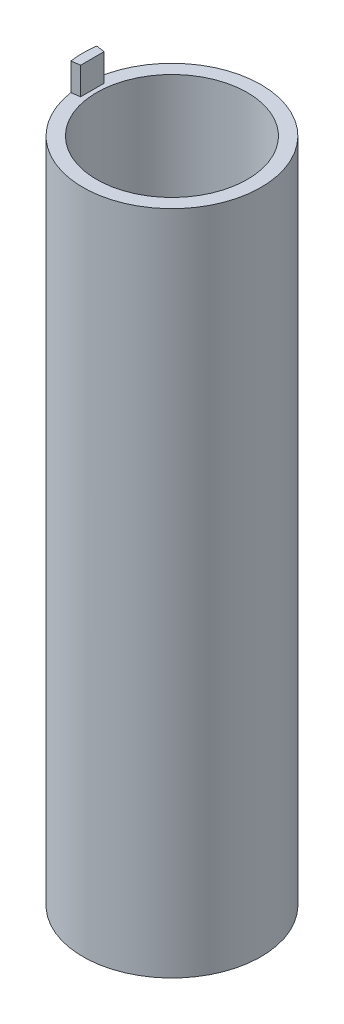
SolidWorks part; units mm, degrees
ref_plane "Front Plane" through (0, 0, 0) normal (0, 0, 1) x (1, 0, 0)
ref_plane "Top Plane" through (0, 0, 0) normal (0, 1, 0) x (1, 0, 0)
ref_plane "Right Plane" through (0, 0, 0) normal (1, 0, 0) x (0, 0, -1)
sketch "Sketch1" plane through (0, 0, 0) normal (0, 1, 0) x (1, 0, 0)
  circle A0 centre (0, 0) radius 17.4625
  circle A1 centre (0, 0) radius 20.6375
  dimension "D1" = 34.925
  dimension "D2" = 3.175
extrude "Boss-Extrude1" add sketch "Sketch1" along normal blind 152.4
sketch "Sketch2" plane through (0, 0, 0) normal (0, -1, 0) x (-1, 0, 0)
  circle A0 centre (0, 0) radius 20.6375
  circle A1 centre (0, 0) radius 20.6375 construction
extrude "Boss-Extrude2" add sketch "Sketch2" along normal blind 2
sketch "Sketch3" plane through (0, 0, 0) normal (0, 0, 1) x (1, 0, 0)
  line L0 (-20.6375, 152.4) -> (-20.6375, 158.75)
  line L1 (-20.6375, 158.75) -> (-18.6375, 158.75)
  line L2 (0, 152.4) -> (0, 163.3315) construction
  line L3 (17.4625, 152.4) -> (-17.4625, 152.4) construction
  line L4 (0, 163.3315) -> (-15.24, 163.3315) construction
  line L5 (0, 160.8381) -> (-15.9385, 160.8381) construction
  line L8 (-18.6375, 158.75) -> (-18.6375, 152.4)
  line L9 (-18.6375, 152.4) -> (-20.6375, 152.4)
  line L10 (20.6375, 152.4) -> (-20.6375, 152.4) construction
  point P2 (0, 0)
  dimension "D1" = 2
  dimension "D2" = 15.24
  dimension "D3" = 15.9385
  dimension "D5" = 6.35
sketch "Sketch4" plane through (0, 152.4, 0) normal (0, 1, 0) x (1, 0, 0)
  line L0 (-18.6375, 0) -> (-20.6375, 0) construction
  arc A0 (-17.2768, -2.54) -> (-17.2768, 2.54) centre (0, 0) cw
  circle A1 centre (0, 0) radius 17.4625 construction
  circle A2 centre (0, 0) radius 17.4625 construction
  point P3 (-17.4625, 0)
  dimension "D1" = 5.08
sweep "Sweep1" add profiles "Sketch3" path "Sketch4"
ref_plane "Plane1" through (-18.4393, 0, 0) normal (1, 0, 0) x (0, 0, -1)
ref_plane "Plane2" through (-16.2168, 0, 0) normal (1, 0, 0) x (0, 0, -1)
sketch "Sketch9" plane through (-18.4393, 0, 0) normal (1, 0, 0) x (0, 0, -1)
  line L1 (-2.7109, 158.75) -> (2.7109, 158.75)
  line L2 (-2.7109, 158.75) -> (-2.7109, 152.4)
  line L3 (-2.7109, 152.4) -> (2.7109, 152.4)
  line L4 (2.7109, 158.75) -> (2.7109, 152.4)
extrude "Boss-Extrude3" add sketch "Sketch9" against normal up to surface up to face at (-18.5384, 155.575, 0)
